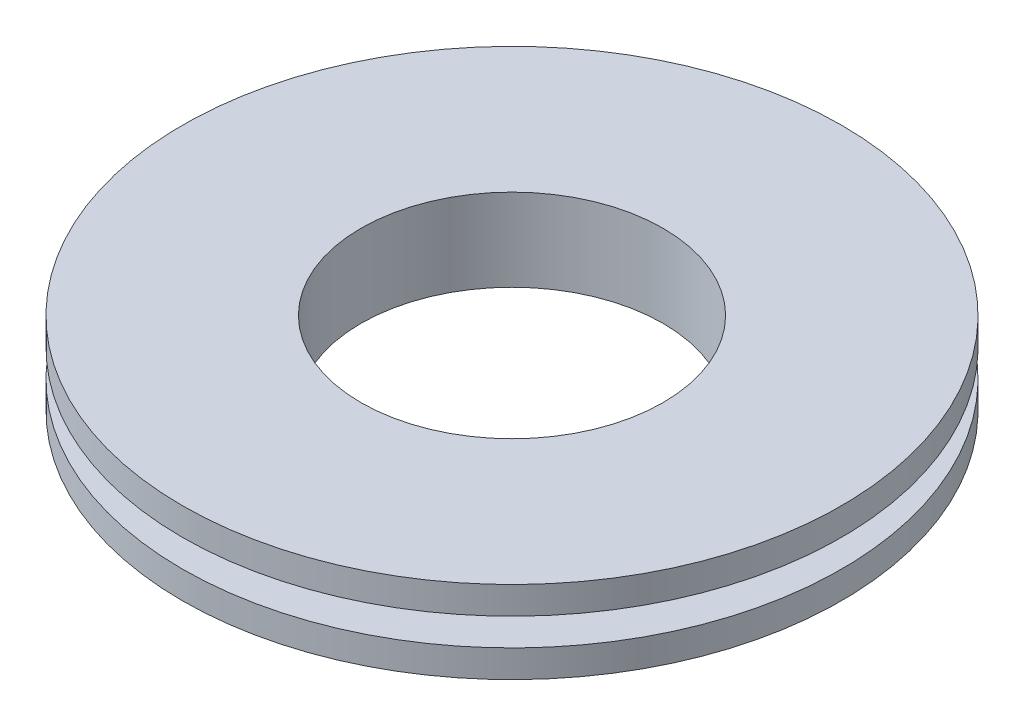
SolidWorks part; units mm, degrees
ref_plane "Front Plane" through (0, 0, 0) normal (0, 0, 1) x (1, 0, 0)
ref_plane "Top Plane" through (0, 0, 0) normal (0, 1, 0) x (1, 0, 0)
ref_plane "Right Plane" through (0, 0, 0) normal (1, 0, 0) x (0, 0, -1)
sketch "Sketch1" plane through (0, 0, 0) normal (0, 1, 0) x (1, 0, 0)
  circle A0 centre (0, 0) radius 5.5
  circle A1 centre (0, 0) radius 10
  dimension "D1" = 11
  dimension "D2" = 20
extrude "Boss-Extrude1" add sketch "Sketch1" along normal blind 3
sketch "Sketch2" plane through (0, 3, 0) normal (0, 1, 0) x (1, 0, 0)
  circle A0 centre (0, 0) radius 12
  circle A1 centre (0, 0) radius 10
  dimension "D1" = 20
  dimension "D2" = 24
extrude "Boss-Extrude2" add sketch "Sketch2" against normal blind 1
sketch "Sketch3" plane through (0, 0, 0) normal (0, -1, 0) x (1, 0, 0)
  circle A0 centre (0, 0) radius 10
  circle A1 centre (0, 0) radius 12
  dimension "D1" = 24
  dimension "D2" = 20
extrude "Boss-Extrude3" add sketch "Sketch3" against normal blind 1
fillet "Fillet2" radius 0.5 2 edges at (0, 2, 10) (0, 1, -10)
